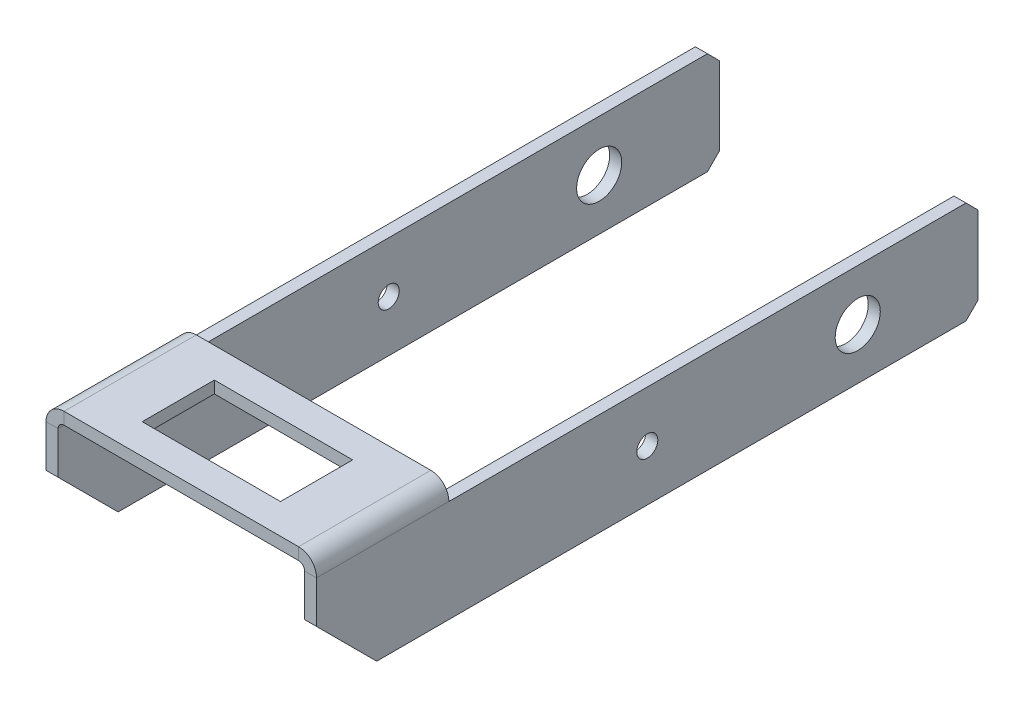
SolidWorks part; units mm, degrees
note: The reader was unsure of these and kept them because the rebuilt part matched: flange length of "Edge-Flange1".
ref_plane "Front Plane" through (0, 0, 0) normal (0, 0, 1) x (1, 0, 0)
ref_plane "Top Plane" through (0, 0, 0) normal (0, 1, 0) x (1, 0, 0)
ref_plane "Right Plane" through (0, 0, 0) normal (1, 0, 0) x (0, 0, -1)
sketch "Sketch1" plane through (0, 0, 0) normal (0, 1, 0) x (1, 0, 0)
  line L1 (0, 0) -> (45, 0)
  line L2 (0, 0) -> (0, 22)
  line L3 (0, 22) -> (45, 22)
  line L4 (45, 0) -> (45, 22)
  dimension "D1" = 22
  dimension "D2" = 45
base flange "Base-Flange1" sketch "Sketch1" thickness 2 reverse thickness direction yes parameters "D1"=1
edge flange "Edge-Flange1" sketch "Sketch22" flange profiles "Sketch22", "Sketch23" flange angle 90 flange length 20 flange position material inside bend radius 1 thickness 2 relief rectangular parameters "D6"=10, "D8"=1
sketch "Sketch22" plane through (45, 0, 0) normal (1, 0, 0) x (0, 0, 1)
  line L0 (0, 0) -> (-22, 0) construction
  line L1 (0, 0) -> (-110, 0)
  line L2 (-110, 0) -> (-110, 18)
  line L3 (-110, 18) -> (0, 18)
  line L4 (0, 18) -> (0, 0)
  dimension "D1" = 110
sketch "Sketch23" plane through (0, 0, 0) normal (-1, 0, 0) x (0, 0, -1)
  line L0 (22, 0) -> (0, 0) construction
  line L1 (110, 0) -> (0, 0)
  line L2 (0, 0) -> (0, 18)
  line L3 (0, 18) -> (110, 18)
  line L4 (110, 18) -> (110, 0)
  dimension "D1" = 110
bend "EdgeBend1" bend radius 1 bend angle 90 parameters "D5"=1
bend "EdgeBend2" bend radius 1 bend angle 90 parameters "D5"=2
sketch "Sketch24" plane through (45, 0, 0) normal (1, 0, 0) x (0, 0, -1)
  line L0 (110, -9.5) -> (90, -9.5) construction
  line L1 (110, -18) -> (110, -1) construction
  line L2 (0, -1) -> (0, -18) construction
  circle A0 centre (90, -9.5) radius 3.75
  dimension "D1" = 7.5
  dimension "D2" = 90
extrude "Cut-Extrude1" cut sketch "Sketch24" against normal blind 10 normal cut yes
sketch "Sketch25" plane through (0, 0, 0) normal (-1, 0, 0) x (0, 0, 1)
  line L0 (-110, -9.5) -> (-90, -9.5) construction
  line L1 (-110, -1) -> (-110, -18) construction
  line L2 (0, -18) -> (0, -1) construction
  circle A0 centre (-90, -9.5) radius 3.75
  dimension "D1" = 7.5
  dimension "D2" = 90
extrude "Cut-Extrude2" cut sketch "Sketch25" against normal blind 10 normal cut yes
sketch "Sketch26" plane through (0, 0, 0) normal (-1, 0, 0) x (0, 0, 1)
sketch "Sketch28" plane through (0, 0, 0) normal (-1, 0, 0) x (0, 0, 1)
  line L0 (-110, -9.5) -> (-55, -9.5) construction
  line L1 (-110, 0) -> (-110, -18) construction
  line L2 (-110, -1) -> (-110, -18) construction
  circle A0 centre (-55, -9.5) radius 1.75
  dimension "D1" = 55
  dimension "D2" = 3.5
extrude "Cut-Extrude3" cut sketch "Sketch28" against normal through all normal cut yes
sketch "Sketch29" plane through (0, 2, 0) normal (0, 1, 0) x (1, 0, 0)
  line L0 (22.5, 22) -> (22.5, 0) construction
  line L1 (0, 22) -> (45, 22) construction
  line L2 (3, 0) -> (42, 0) construction
  line L4 (11, 5) -> (34, 5)
  line L5 (11, 5) -> (11, 17)
  line L6 (11, 17) -> (34, 17)
  line L7 (34, 5) -> (34, 17)
  line L8 (11, 5) -> (34, 17) construction
  line L9 (11, 17) -> (34, 5) construction
  point P6 (22.5, 11)
  dimension "D1" = 23
  dimension "D2" = 12
extrude "Cut-Extrude4" cut sketch "Sketch29" against normal blind 10 normal cut yes
chamfer "Chamfer1" distance 2 angle 45 4 edges at (44, -18, -110) (44, -1, -110) (1, -18, -110) (1, -1, -110)
chamfer "Chamfer2" distance 10 angle 45 2 edges at (1, -18, 0) (44, -18, 0)
sketch "Bend-Lines1" [suppressed] plane through (0, 0, 0) normal (0, 1, 0) x (1, 0, 0)
sketch "Bounding-Box1" [suppressed] plane through (0, 0, 0) normal (0, 1, 0) x (1, 0, 0)
sheet metal parameters "Sheet-Metal1" thickness 2 parameters "D1"=0.7366
flat pattern "Flat-Pattern1" [suppressed]
sketch "Bend-Lines2" plane through (0, 0, 0) normal (0, 1, 0) x (1, 0, 0)
sketch3d "Bounding-Box2" [suppressed]
  line L0 (-40, 22, 0) -> (0, 22, 0) construction
  line L1 (-40, 0, 0) -> (0, 0, 0) construction
  line L2 (-40, 22, 0) -> (-40, 0, 0) construction
  line L3 (0, 22, 0) -> (0, 0, 0) construction
sheet metal parameters "Sheet-Metal2" thickness 2 parameters "D1"=0.7366
flat pattern "Flat-Pattern1"
sketch "Bend-Lines2" plane through (0, 0, 0) normal (0, -1, 0) x (-1, 0, 0)
  line L0 (-1.4292, 0) -> (-1.4292, 22) construction
  line L1 (-38.5708, 22) -> (-38.5708, 0) construction
  line L2 (-1.4292, 0) -> (-1.4292, 22) construction
  line L3 (-38.5708, 22) -> (-38.5708, 0) construction
sketch3d "Bounding-Box2" [suppressed]
  line L0 (17.1416, 0, 0) -> (17.1416, 110, 0) construction
  line L1 (-57.1416, 0, 0) -> (-57.1416, 110, 0) construction
  line L2 (17.1416, 0, 0) -> (-57.1416, 0, 0) construction
  line L3 (17.1416, 110, 0) -> (-57.1416, 110, 0) construction
bend of the flat pattern "Flatten-<EdgeBend1>1"
bend of the flat pattern "Flatten-<EdgeBend2>1"
sheet metal parameters "Sheet-Metal3" thickness 2 parameters "D1"=0.7366
flat pattern "Flat-Pattern1"
sketch "Bend-Lines2" plane through (0, 0, 0) normal (0, -1, 0) x (-1, 0, 0)
  line L0 (-1.4292, 0) -> (-1.4292, 22) construction
  line L1 (-38.5708, 22) -> (-38.5708, 0) construction
  line L2 (-1.4292, 0) -> (-1.4292, 22) construction
  line L3 (-38.5708, 22) -> (-38.5708, 0) construction
sketch3d "Bounding-Box2" [suppressed]
  line L0 (17.1416, 0, 0) -> (17.1416, 110, 0) construction
  line L1 (-57.1416, 0, 0) -> (-57.1416, 110, 0) construction
  line L2 (17.1416, 0, 0) -> (-57.1416, 0, 0) construction
  line L3 (17.1416, 110, 0) -> (-57.1416, 110, 0) construction
bend of the flat pattern "Flatten-<EdgeBend1>1"
bend of the flat pattern "Flatten-<EdgeBend2>1"
sheet metal parameters "Sheet-Metal4" thickness 2 parameters "D1"=0.7366
flat pattern "Flat-Pattern1" [suppressed]
sketch "Bend-Lines2" plane through (0, 0, 0) normal (0, -1, 0) x (-1, 0, 0)
  line L0 (-1.4292, 0) -> (-1.4292, 22) construction
  line L1 (-38.5708, 22) -> (-38.5708, 0) construction
  line L2 (-1.4292, 0) -> (-1.4292, 22) construction
  line L3 (-38.5708, 22) -> (-38.5708, 0) construction
sketch3d "Bounding-Box2" [suppressed]
  line L0 (17.1416, 0, 0) -> (17.1416, 110, 0) construction
  line L1 (-57.1416, 0, 0) -> (-57.1416, 110, 0) construction
  line L2 (17.1416, 0, 0) -> (-57.1416, 0, 0) construction
  line L3 (17.1416, 110, 0) -> (-57.1416, 110, 0) construction
bend of the flat pattern "Flatten-<EdgeBend1>1"
bend of the flat pattern "Flatten-<EdgeBend2>1"
sketch "Sketch26-1" [suppressed] plane through (0.8584, 2, 0) normal (0, 1, 0) x (0, 0, 1)
sheet metal parameters "Sheet-Metal5" thickness 2 parameters "D1"=0.7366
flat pattern "Flat-Pattern1" [suppressed]
sketch "Bend-Lines2" plane through (0, 0, 0) normal (0, -1, 0) x (-1, 0, 0)
  line L0 (-1.4292, 0) -> (-1.4292, 22) construction
  line L1 (-38.5708, 22) -> (-38.5708, 0) construction
  line L2 (-1.4292, 0) -> (-1.4292, 22) construction
  line L3 (-38.5708, 22) -> (-38.5708, 0) construction
sketch3d "Bounding-Box2" [suppressed]
  line L0 (17.1416, 0, 0) -> (17.1416, 110, 0) construction
  line L1 (-57.1416, 0, 0) -> (-57.1416, 110, 0) construction
  line L2 (17.1416, 0, 0) -> (-57.1416, 0, 0) construction
  line L3 (17.1416, 110, 0) -> (-57.1416, 110, 0) construction
bend of the flat pattern "Flatten-<EdgeBend1>1"
bend of the flat pattern "Flatten-<EdgeBend2>1"
sketch "Sketch26-1" [suppressed] plane through (0.8584, 2, 0) normal (0, 1, 0) x (0, 0, 1)
sheet metal parameters "Sheet-Metal6" thickness 2 parameters "D1"=0.7366
flat pattern "Flat-Pattern1" [suppressed]
sketch "Bend-Lines2" plane through (0, 0, 0) normal (0, -1, 0) x (-1, 0, 0)
  line L0 (-1.4292, 0) -> (-1.4292, 22) construction
  line L1 (-43.5708, 22) -> (-43.5708, 0) construction
  line L2 (-1.4292, 0) -> (-1.4292, 22) construction
  line L3 (-43.5708, 22) -> (-43.5708, 0) construction
sketch3d "Bounding-Box2" [suppressed]
  line L0 (17.1416, 0, 0) -> (17.1416, 110, 0) construction
  line L1 (-62.1416, 0, 0) -> (-62.1416, 110, 0) construction
  line L2 (17.1416, 0, 0) -> (-62.1416, 0, 0) construction
  line L3 (17.1416, 110, 0) -> (-62.1416, 110, 0) construction
bend of the flat pattern "Flatten-<EdgeBend1>1"
bend of the flat pattern "Flatten-<EdgeBend2>1"
sketch "Sketch26-1" plane through (0.8584, 2, 0) normal (0, 1, 0) x (0, 0, 1)
